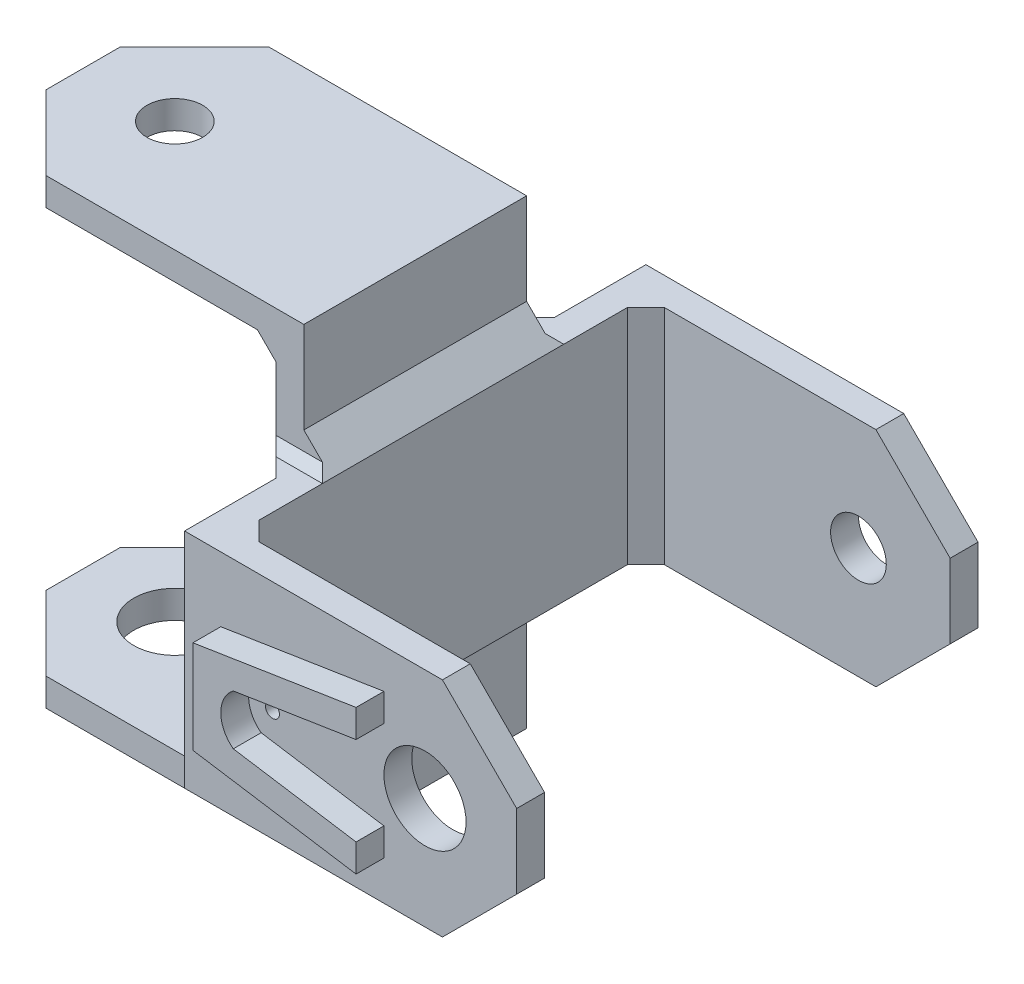
SolidWorks part; units mm, degrees
ref_plane "前视基准面" through (0, 0, 0) normal (0, 0, 1) x (1, 0, 0)
ref_plane "上视基准面" through (0, 0, 0) normal (0, 1, 0) x (1, 0, 0)
ref_plane "右视基准面" through (0, 0, 0) normal (1, 0, 0) x (0, 0, -1)
sketch "草图1" plane through (0, 0, 0) normal (0, 0, 1) x (1, 0, 0)
  line L0 (77.245, 23.2022) -> (113.025, 23.2022)
  line L1 (113.025, 23.2022) -> (113.025, -26.4978)
  line L2 (113.025, -26.4978) -> (77.245, -26.4978)
  line L3 (77.245, -26.4978) -> (77.245, -23.4978)
  line L4 (77.245, -23.4978) -> (110.025, -23.4978)
  line L5 (110.025, -23.4978) -> (110.025, 20.2022)
  line L6 (110.025, 20.2022) -> (77.245, 20.2022)
  line L7 (77.245, 20.2022) -> (77.245, 23.2022)
  line L9 (91.4217, 18.2022) -> (73.506, 18.2022) construction
  line L11 (90.025, -26.7978) -> (90.025, -22.7978) construction
  line L13 (72.5738, 20.2022) -> (90.4895, 20.2022) construction
  dimension "D1" = 44.7
  dimension "D2" = 3
  dimension "D3" = 20
  dimension "D4" = 3
  dimension "D5" = 3
  dimension "D6" = 35.78
  dimension "D7" = 35.78
extrude "凸台-拉伸1" add sketch "草图1" along normal mid plane 24
chamfer "倒角1" distance 2 2 edges at (110.025, 20.2022, 0) (110.025, -23.4978, 0)
sketch "草图2" plane through (0, 23.2022, 0) normal (0, 1, 0) x (1, 0, 0)
  circle A0 centre (87.125, 0) radius 3
  dimension "D1" = 6
extrude "切除-拉伸1" cut sketch "草图2" against normal up to next
sketch "草图3" plane through (0, -26.4978, 0) normal (0, -1, 0) x (1, 0, 0)
  circle A0 centre (87.125, 0) radius 4.425
  dimension "D1" = 8.85
extrude "切除-拉伸2" cut sketch "草图3" against normal up to next
sketch "草图4" plane through (0, -26.4978, 0) normal (0, -1, 0) x (1, 0, 0)
  line L0 (87.125, 0) -> (106.125, 0) construction
  line L7 (91.55, -1000.6505) -> (91.55, 48999.3495) construction
  line L10 (91.55, 4.775) -> (91.55, 7.775)
  line L11 (91.55, 7.775) -> (109.125, 5.0181)
  line L12 (109.125, 5.0181) -> (109.125, -5.0181)
  line L13 (109.125, -5.0181) -> (91.55, -7.775)
  line L14 (91.55, -7.775) -> (91.55, -4.775)
  line L15 (91.55, 4.775) -> (104.7778, 2.7)
  line L16 (91.55, -4.775) -> (104.7778, -2.7)
  circle A3 centre (87.125, 0) radius 4.425 construction
  arc A4 (104.7778, 2.7) -> (104.7778, -2.7) centre (102.7458, 0) cw
  point P7 (106.125, 0)
  dimension "D9" = 2.7
  dimension "D3" = 3.3792
  dimension "D1" = 19
  dimension "D2" = 9.55
  dimension "D4" = 13.2278
  dimension "D6" = 3
  dimension "D7" = 3
  dimension "D8" = 3
extrude "凸台-拉伸2" add sketch "草图4" along normal blind 3
sketch "草图5" plane through (0, -26.4978, 0) normal (0, -1, 0) x (1, 0, 0)
  line L0 (77.245, -12) -> (113.025, -12) construction
  line L3 (91.55, -997.3079) -> (91.55, 49002.6918) construction
  line L5 (91.55, -201000.6505) -> (91.55, 248999.3495) construction
  point P0 (103.55, 0)
  dimension "D1" = 12
  dimension "D2" = 12
hole_wizard "大小mm 暗销孔1" positions "3D草图1" profile "草图6" hole size "Ø1.5" standard "GB"
sketch3d "3D草图1"
  point P0 (103.55, -26.4978, 0)
sketch "草图6" plane through (103.55, -26.4978, 0) normal (1, 0, 0) x (0, 0, -1)
  line L0 (0, 0) -> (0, 10.4506)
  line L1 (0, 10.4506) -> (0.75, 10)
  line L2 (0.75, 10) -> (0.75, 0)
  line L5 (0.75, 0) -> (0, 0)
  line L10 (0, 10.4506) -> (-0.75, 10) construction
  line L11 (0, -6.35) -> (0, 107.95) construction
  dimension "孔直径" = 1.5
  dimension "孔深度" = 10
  dimension "导头角度" = 118
sketch "草图7" plane through (113.025, 0, 0) normal (1, 0, 0) x (0, 0, -1)
  line L0 (-12, 23.2022) -> (12, 23.2022) construction
  line L1 (-24.85, 10.3522) -> (24.85, 10.3522)
  line L2 (-24.85, 10.3522) -> (-24.85, -13.6478)
  line L3 (-24.85, -13.6478) -> (24.85, -13.6478)
  line L4 (24.85, 10.3522) -> (24.85, -13.6478)
  line L5 (-24.85, 10.3522) -> (24.85, -13.6478) construction
  line L6 (-24.85, -13.6478) -> (24.85, 10.3522) construction
  line L7 (12, -26.4978) -> (12, 23.2022) construction
  point P0 (0, -1.6478)
  point P7 (0, 23.2022)
  point P10 (12, -1.6478)
  dimension "D1" = 24
  dimension "D2" = 49.7
extrude "凸台-拉伸3" add sketch "草图7" along normal blind 3
sketch "草图8" plane through (116.025, 0, 0) normal (1, 0, 0) x (0, 0, -1)
  line L0 (-24.85, -13.6478) -> (24.85, -13.6478) construction
  line L1 (-24.85, 10.3522) -> (-21.85, 10.3522)
  line L2 (-24.85, 10.3522) -> (-24.85, -13.6478)
  line L3 (-24.85, -13.6478) -> (-21.85, -13.6478)
  line L4 (-21.85, 10.3522) -> (-21.85, -13.6478)
  line L5 (24.85, -13.6478) -> (24.85, 10.3522) construction
  line L6 (24.85, 10.3522) -> (21.85, 10.3522)
  line L7 (24.85, 10.3522) -> (24.85, -13.6478)
  line L8 (24.85, -13.6478) -> (21.85, -13.6478)
  line L9 (21.85, 10.3522) -> (21.85, -13.6478)
  dimension "D1" = 3
  dimension "D2" = 3
  dimension "D3" = 24
extrude "凸台-拉伸4" add sketch "草图8" along normal blind 32.78
sketch "草图9" plane through (0, 0, -24.85) normal (0, 0, -1) x (-1, 0, 0)
  line L0 (-148.805, -13.6478) -> (-148.805, 10.3522) construction
  line L1 (-148.805, 10.3522) -> (-113.025, 10.3522) construction
  circle A0 centre (-138.925, -1.6478) radius 3
  dimension "D2" = 6
  dimension "D1" = 9.88
  dimension "D3" = 12
extrude "切除-拉伸3" cut sketch "草图9" against normal up to next
sketch "草图10" plane through (0, 0, 24.85) normal (0, 0, 1) x (1, 0, 0)
  line L0 (148.805, 10.3522) -> (148.805, -13.6478) construction
  line L3 (148.805, 10.3522) -> (113.025, 10.3522) construction
  point P0 (138.925, -1.6478)
  dimension "D1" = 9.88
  dimension "D2" = 12
sketch "草图12" plane through (0, 0, 24.85) normal (0, 0, 1) x (1, 0, 0)
  circle A0 centre (138.925, -1.6478) radius 4.425
  dimension "D1" = 8.85
extrude "切除-拉伸4" cut sketch "草图12" against normal up to next
sketch "草图13" plane through (0, 0, 24.85) normal (0, 0, 1) x (1, 0, 0)
  line L0 (138.925, -1.6478) -> (116.925, -1.6478) construction
  line L1 (116.925, 3.3703) -> (116.925, -6.6659) construction
  line L2 (116.925, 3.3703) -> (116.925, -6.6659)
  line L3 (116.925, -6.6659) -> (134.5, -9.4228)
  line L4 (134.5, -9.4228) -> (134.5, -6.4228)
  line L5 (134.5, 6.1272) -> (116.925, 3.3703)
  line L6 (-861.075, -1.6478) -> (49138.925, -1.6478) construction
  line L8 (134.5, 3.1272) -> (134.5, 6.1272)
  line L10 (134.5, 3.1272) -> (121.2721, 1.0522)
  line L11 (134.5, -6.4228) -> (121.2721, -4.3478)
  line L12 (134.5, -1001.6478) -> (134.5, 48998.3522) construction
  arc A1 (121.2721, 1.0522) -> (121.2721, -4.3478) centre (123.3043, -1.6478) ccw
  circle A3 centre (138.925, -1.6478) radius 4.425 construction
  point P12 (119.925, -1.6478)
  dimension "D7" = 3
  dimension "D6" = 3.3793
  dimension "D1" = 13.2279
  dimension "D4" = 9.55
  dimension "D5" = 3
  dimension "D8" = 2.7
extrude "凸台-拉伸5" add sketch "草图13" along normal blind 3
sketch "草图15" plane through (0, 0, 24.85) normal (0, 0, 1) x (1, 0, 0)
  point P0 (122.495, -1.6478)
  point P1 (122.495, -1.6478)
  point P2 (138.925, -1.6478)
  dimension "D1" = 16.43
hole_wizard "大小mm 暗销孔2" positions "3D草图2" profile "草图16" hole size "Ø1.5" standard "GB"
sketch3d "3D草图2"
  point P0 (122.495, -1.6478, 24.85)
sketch "草图16" plane through (122.495, -1.6478, 24.85) normal (1, 0, 0) x (0, -1, 0)
  line L0 (0, 0) -> (0, 10.4506)
  line L1 (0, 10.4506) -> (0.75, 10)
  line L2 (0.75, 10) -> (0.75, 0)
  line L5 (0.75, 0) -> (0, 0)
  line L10 (0, 10.4506) -> (-0.75, 10) construction
  line L11 (0, -6.35) -> (0, 107.95) construction
  dimension "孔直径" = 1.5
  dimension "孔深度" = 10
  dimension "导头角度" = 118
chamfer "倒角2" distance 2 angle 45 2 edges at (116.025, -1.6478, 21.85) (116.025, -1.6478, -21.85)
chamfer "倒角3" distance 3 angle 45 2 edges at (113.025, 10.3522, 0) (113.025, -13.6478, 0)
chamfer "倒角4" distance 3 angle 45 2 edges at (113.025, -1.6478, 12) (113.025, -1.6478, -12)
chamfer "倒角5" distance 1 angle 45 4 edges at (113.025, 10.3522, 12) (113.025, 10.3522, -12) (113.025, -13.6478, -12) (113.025, -13.6478, 12)
chamfer "倒角6" distance 8 angle 45 8 edges at (148.805, 10.3522, 23.35) (148.805, -13.6478, 23.35) (148.805, -13.6478, -23.35) (148.805, 10.3522, -23.35) (77.245, -24.9978, 12) (77.245, -24.9978, -12) (77.245, 21.7022, -12) (77.245, 21.7022, 12)
